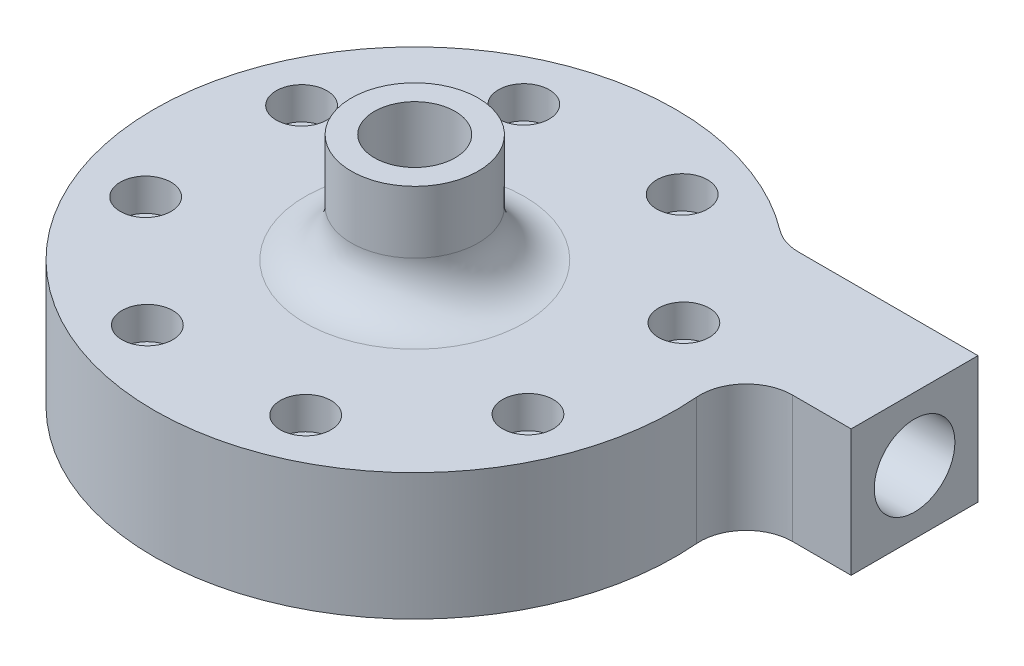
SolidWorks part; units mm, degrees
material "1060 Alloy"
ref_plane "Front" through (0, 0, 0) normal (0, 0, 1) x (1, 0, 0)
ref_plane "Top" through (0, 0, 0) normal (0, 1, 0) x (1, 0, 0)
ref_plane "Right" through (0, 0, 0) normal (1, 0, 0) x (0, 0, -1)
sketch "Sketch1" plane through (0, 0, 0) normal (0, 1, 0) x (1, 0, 0)
  line L0 (0, 0) -> (2.6693, 30.5101) construction
  line L1 (2.6693, 30.5101) -> (60.9409, 35.6082) construction
  line L2 (9.0461, 29.2602) -> (60.9409, 29.2602) construction
  line L3 (14.512, 26.9702) -> (60.9409, 22.9082) construction
  line L4 (0, 0) -> (56.2352, -4.9199) construction
  line L5 (14.512, 31.5462) -> (14.512, 29.2602) construction
  line L6 (14.512, 29.2602) -> (14.512, 26.9702) construction
  line L7 (60.9409, 29.2602) -> (60.9409, 35.6082) construction
  line L8 (60.9409, 29.2602) -> (60.9409, 22.9082) construction
  line L9 (78.9409, 29.2602) -> (78.9409, 42.9915)
  line L10 (78.9409, 37.9915) -> (60.9409, 37.9915) construction
  line L11 (78.9409, 37.9915) -> (78.9409, 20.529) construction
  line L12 (78.9409, 20.529) -> (60.9409, 20.529) construction
  line L13 (60.9409, 37.9915) -> (60.9409, 20.529) construction
  line L14 (78.9409, 42.9915) -> (40.0937, 42.9915)
  line L15 (78.9409, 29.2602) -> (78.9409, 15.529)
  line L16 (78.9409, 15.529) -> (66.2196, 15.529)
  arc A0 (34.06, 45.0169) -> (56.2543, 4.6969) centre (0, 0) ccw
  circle A1 centre (0, 0) radius 30.6267 construction
  arc A2 (66.2196, 15.529) -> (56.2543, 4.6969) centre (66.2196, 5.529) ccw
  arc A3 (40.0937, 42.9915) -> (34.06, 45.0169) centre (40.0937, 52.9915) cw
  dimension "D1" = 112.9
  dimension "D2" = 61.2534
  dimension "D13" = 10
  dimension "D4" = 2.286
  dimension "D3" = 2.29
  dimension "D5" = 5
  dimension "D6" = 5
  dimension "D7" = 5
  dimension "D8" = 12.7
  dimension "D9" = 17.4625
  dimension "D10" = 18
  dimension "D11" = 5
  dimension "D12" = 5
extrude "main body" add sketch "Sketch1" along normal blind 27.4625
ref_plane "body midsection" through (0, 13.7313, 0) normal (0, 1, 0) x (1, 0, 0)
sketch "Sketch2" plane through (0, 0, 0) normal (0, 0, 1) x (1, 0, 0)
  line L0 (0, 27.4625) -> (0, 0) construction
  line L1 (56.45, 27.4625) -> (-56.45, 27.4625) construction
  line L2 (0, 27.4625) -> (5.4102, 27.4625)
  line L3 (0, 12.1864) -> (30.6267, 12.1864) construction
  line L4 (30.6267, 15.2761) -> (5.4102, 25.9331)
  line L5 (5.4102, 27.4625) -> (5.4102, 25.9331)
  line L6 (30.6267, 15.2761) -> (30.6267, 0)
  line L7 (30.6267, 15.2761) -> (30.6267, 12.1864) construction
  line L8 (58.025, 13.7313) -> (-58.025, 13.7313) construction
  line L10 (-56.45, 0) -> (56.45, 0) construction
  line L11 (30.6267, 0) -> (0, 0)
  line L12 (0, 0) -> (0, 27.4625)
  line L13 (30.6267, 13.7313) -> (26.6319, 13.7313) construction
  line L14 (0, 13.7313) -> (26.6319, 13.7313) construction
  line L15 (26.6319, 13.7313) -> (26.6319, 16.9644) construction
  line L16 (26.6319, 16.9644) -> (0, 16.9644) construction
  dimension "D1" = 30.6267
  dimension "D3" = 26.6319
  dimension "D5" = 5.4102
  dimension "D2" = 4.778
  dimension "D6" = 13.7467
revolve "main chamber" cut sketch "Sketch2" angle 360 about L12
sketch "Sketch4" plane through (0, 0, 0) normal (0, 0, 1) x (1, 0, 0)
  line L0 (5.4102, 27.4625) -> (5.4102, 35.9331)
  line L2 (5.4102, 35.9331) -> (8.7313, 35.9331)
  line L3 (8.7313, 35.9331) -> (8.7313, 50.9331)
  line L4 (8.7313, 50.9331) -> (13.7313, 50.9331)
  line L5 (13.7313, 50.9331) -> (13.7313, 37.4625)
  line L7 (0, 0) -> (0, 49.2593) construction
  line L8 (56.45, 0) -> (-56.45, 0) construction
  line L9 (5.4102, 25.9331) -> (-5.4102, 25.9331) construction
  line L10 (5.4102, 27.4625) -> (23.7313, 27.4625)
  arc A0 (13.7313, 37.4625) -> (23.7313, 27.4625) centre (23.7313, 37.4625) ccw
  dimension "D5" = 10
  dimension "D1" = 10
  dimension "D2" = 8.7313
  dimension "D3" = 5
  dimension "D4" = 15
revolve "inlet" add sketch "Sketch4" angle 360 about L7
sketch "Sketch3" plane through (0, 13.7313, 0) normal (0, 1, 0) x (1, 0, 0)
  line L0 (2.6693, 30.5101) -> (60.9409, 35.6082)
  line L2 (60.9409, 29.2602) -> (2.5599, 29.2602)
  line L3 (0, 0) -> (2.6693, 30.5101) construction
  line L4 (2.5599, 29.2602) -> (2.6693, 30.5101)
  line L5 (60.9409, 35.6082) -> (60.9409, 37.9915)
  line L6 (60.9409, 37.9915) -> (78.9409, 37.9915)
  line L7 (78.9409, 37.9915) -> (78.9409, 29.2602)
  line L8 (78.9409, 29.2602) -> (60.9409, 29.2602)
revolve "expansion cone and outlet" cut sketch "Sketch3" angle 360 about L2
sketch "Sketch5" plane through (0, 27.4625, 0) normal (0, 1, 0) x (1, 0, 0)
  line L1 (16.6948, 41.1957) -> (40.9348, 17.3248) construction
  line L3 (9.0461, 29.2602) -> (60.9409, 29.2602) construction
  circle A0 centre (0, 0) radius 44.45 construction
  circle A1 centre (40.9348, 17.3248) radius 2.9766
  circle A2 centre (0, 0) radius 44.45 construction
  circle A3 centre (41.1957, -16.6948) radius 2.9766
  circle A4 centre (0, 0) radius 44.45 construction
  circle A5 centre (17.3248, -40.9348) radius 2.9766
  circle A6 centre (0, 0) radius 44.45 construction
  circle A7 centre (-16.6948, -41.1957) radius 2.9766
  circle A8 centre (0, 0) radius 44.45 construction
  circle A9 centre (-40.9348, -17.3248) radius 2.9766
  circle A10 centre (0, 0) radius 44.45 construction
  circle A11 centre (-41.1957, 16.6948) radius 2.9766
  circle A12 centre (0, 0) radius 44.45 construction
  circle A13 centre (-17.3248, 40.9348) radius 2.9766
  circle A14 centre (0, 0) radius 44.45 construction
  circle A15 centre (16.6948, 41.1957) radius 2.9766
  point P5 (28.8148, 29.2602)
  point P30 (0, 0)
  dimension "D1" = 88.9
  dimension "D2" = 5.9531
  dimension "D4" = 8
sketch "Sketch6" plane through (0, 27.4625, 0) normal (0, 1, 0) x (1, 0, 0)
  circle A0 centre (40.9348, 17.3248) radius 5.5
  circle A1 centre (41.1957, -16.6948) radius 5.5
  circle A2 centre (17.3248, -40.9348) radius 5.5
  circle A3 centre (-16.6948, -41.1957) radius 5.5
  circle A4 centre (-40.9348, -17.3248) radius 5.5
  circle A5 centre (-41.1957, 16.6948) radius 5.5
  circle A6 centre (-17.3248, 40.9348) radius 5.5
  circle A7 centre (16.6948, 41.1957) radius 5.5
  point P19 (0, 0)
  dimension "D1" = 11
  dimension "D2" = 8
ref_plane "exit axial plane" through (0, 0, -29.2602) normal (0, 0, -1) x (-1, 0, 0)
extrude "bolt clearances" cut sketch "Sketch5" against normal through all
extrude "bolt head clearance" cut sketch "Sketch6" against normal blind 7
equation "\"bearing OD\"= 30mm"
equation "\"bearing ID\"= 10mm"
equation "\"bearing depth\"= 9mm"
equation "\"bearing outer race thickness\"= 1mm"
equation "\"bearing inner race thickness\"= 1mm"
equation "\"bearing bore\"= \"bearing depth\" + 1mm"
equation "\"z\"= 8 \t\t\t'number of blades"
equation "\"de\"= 0.426in\t\t\t'entrance eye diameter"
equation "\"d2\"= 2.097in \t\t\t'outer diameter of the impeller"
equation "\"d_exit\"= 0.18in \t\t'volute throat aka D4"
equation "\"theta\"= 25\t\t\t'angle of blades from inner to outer "
equation "\"b2\"= .07in\t\t\t\t\t\t\t'tip height from disc surface at d2"
equation "\"b1\"= \"b2\" + (\"d2\"/2 - \"de\"/2)*sin(\"theta\") \t\t\t'tip height from disc surface at inlet eye"
equation "\"s\"=\"ce\" - \"z\"*\"s_open\""
equation "\"impeller upper clearance\"= .5mm"
equation "\"impeller horizontal clearance\"= (\"d2\"*1.15 - \"d2\")/2 \t\t'clearance based on D2-D3 ratio for circular volute, ranges 1.15 to 1.2"
equation "\"impeller bottom clearance\"= .5mm"
equation "\"impeller base thickness\"= 2mm"
equation "\"impeller dowel diameter\"= 2mm"
equation "\"impeller bolt head diameter\"= \"m4 head bore diameter\""
equation "\"impeller bolt head depth\"= 4mm"
equation "\"impeller bolt stop depth\"= 3mm"
equation "\"impeller bolt bore\"= \"m4 clearance\""
equation "\"impeller shaft bore depth\"= 12mm"
equation "\"impeller shaft bore\"= 8mm"
equation "\"impeller boss depth\"= \"impeller shaft bore depth\"+\"impeller bolt stop depth\"+\"impeller bolt head depth\"-\"impeller base thickness\""
equation "\"impeller boss diameter\"= \"upper seal ID\""
equation "\"impeller dowel length\"= 2mm*2 + \"impeller shaft bore\""
equation "\"coupler motor shaft hole ID\"= 8mm"
equation "\"coupler OD\"= 17mm"
equation "\"coupler length\"= 25mm"
equation "\"motor OD\"= 64mm"
equation "\"motor shaft diameter\"= 8mm"
equation "\"motor shaft pride\"= 32mm"
equation "\"motor to bearing plate distance\"= \"motor shaft pride\" + 2mm +\"coupler length\"/2"
equation "\"square plate bolt bore\"= 8mm"
equation "\"square plate bolt head diameter\"= 13.5mm"
equation "\"square plate bolt head depth\"= 8mm"
equation "\"square plate bolt pattern diameter\"= 3.5in"
equation "\"motor mount center bore\"= \"coupler OD\"+ 4mm"
equation "\"motor mount post radius\"= ( 3 * \"square plate bolt bore\" ) / 2"
equation "\"motor mount m4 screw hole diameter\"= 4mm"
equation "\"motor mount m4 head diameter\"= 7.25mm"
equation "\"motor mount m4 head depth\"= 4mm"
equation "\"motor mount m4 pattern diamater\"= 30mm"
equation "\"motor mount plate thickness\"= 8mm + \"motor mount m4 head depth\""
equation "\"bearing plate stop ID\"= \"bearing OD\" - 4mm"
equation "\"bearing plate stop depth\"= 3mm"
equation "\"bearing plate thickness\"= \"bearing bore\" + \"bearing plate stop depth\" + \"shaft bearing stop length\""
equation "\"shaft coupler section diameter\"= 8mm"
equation "\"shaft coupler section length\"= \"motor to bearing plate distance\" - \"motor shaft pride\" - 2mm"
equation "\"shaft bearing section diameter\"= \"bearing ID\""
equation "\"shaft bearing section length\"= \"bearing plate stop depth\" + \"bearing depth\""
equation "\"shaft bearing stop diameter\"= \"bearing ID\" + 4mm"
equation "\"shaft bearing stop length\"= 3mm"
equation "\"impeller cavity center height\"= \"impeller bottom clearance\" + \"impeller upper clearance\" + \"impeller center height\""
equation "\"impeller cavity diameter\"= 2 * \"impeller horizontal clearance\" + \"d2\" \t\t\t\t\t\t\t\t\t'called D3 analytically"
equation "\"impeller cavity outer height\"= \"impeller bottom clearance\" + \"impeller upper clearance\" + \"impeller base thickness\" + \"b2\" \t\t'this is height at impeller diameter d2, not at d3"
equation "\"impeller housing thickness\"= \"impeller housing exit threaded diameter\" + 2*\"impeller housing outlet grip\""
equation "\"impeller housing diameter\"= \"square plate bolt pattern diameter\" + 2*\"motor mount post radius\""
equation "\"impeller housing bolt count\"= 8"
equation "\"impeller housing bolt diameter\"= \"m6 clearance\""
equation "\"impeller housing bolt pattern diameter\"= 3.5in"
equation "\"impeller housing threaded inlet diameter\"= 0.6875in \t\t'this is the 11/16 drill size for 1/2 npt fitting"
equation "\"impeller housing threaded inlet depth\"= 15mm"
equation "\"impeller housing exit threaded diameter\"= 0.6875in \t\t'this is the 11/16 drill size for 1/2 npt fitting"
equation "\"impeller housing exit threaded depth\"= 18mm"
equation "\"impeller housing diffuser conical angle\"=10"
equation "\"impeller housing diffuser tangent angle\"=5"
equation "\"impeller housing diffuser final diameter\"= .5in"
equation "\"impeller housing outlet grip\"= 5mm"
equation "\"D1@Sketch1\"=\"impeller housing diameter\""
equation "\"D2@Sketch1\"=\"impeller cavity diameter\""
equation "\"D4@Sketch1\"=\"d_exit\"/2"
equation "\"D5@Sketch1\"=\"impeller housing diffuser tangent angle\""
equation "\"D6@Sketch1\"=\"impeller housing diffuser conical angle\"/2"
equation "\"D7@Sketch1\"=\"impeller housing diffuser conical angle\"/2"
equation "\"D8@Sketch1\"=\"impeller housing diffuser final diameter\""
equation "\"D9@Sketch1\"=\"impeller housing exit threaded diameter\""
equation "\"D10@Sketch1\"=\"impeller housing exit threaded depth\""
equation "\"D11@Sketch1\"=\"impeller housing outlet grip\""
equation "\"D12@Sketch1\"=\"impeller housing outlet grip\""
equation "\"D1@main body\" = \"impeller housing thickness\""
equation "\"D1@Sketch2\"=\"impeller cavity diameter\"/2"
equation "\"D3@Sketch2\"= \"d2\" / 2"
equation "\"D2@Sketch2\"=\"impeller cavity outer height\""
equation "\"D5@Sketch2\"=\"de\"/2"
equation "\"D6@Sketch2\" = \"impeller center height\" + \"impeller bottom clearance\" + \"impeller upper clearance\""
equation "\"de_length\"= 10mm\t\t'entrance eye consistent length"
equation "\"D2@Sketch4\"=\"impeller housing threaded inlet diameter\"/2"
equation "\"D3@Sketch4\"=\"impeller housing outlet grip\""
equation "\"D4@Sketch4\"=\"impeller housing threaded inlet depth\""
equation "\"D1@Sketch5\"=\"impeller housing bolt pattern diameter\""
equation "\"D2@Sketch5\"=\"m6 clearance\""
equation "\"end mill size\"= 0.375in\t'for 3/8 endmill"
equation "\"ae\"= 3.14*(\"de\"^2)/4\t\t'entrance eye area'"
equation "\"ce\"= 3.14*\"de\"\t\t'entrance eye circumference"
equation "\"av_ratio\"= .325\t\t'ratio of av/ae at N_s of 470, range is .275 to .375, .325 ideal. High ratio means bigger area means smaller blades"
equation "\"av\"= \"ae\"*\"av_ratio\"\t\t'area between just two blades"
equation "\"s_open\"= \"av\"/\"b1\"\t\t'width of open area"
equation "\"impeller center height\"= \"impeller base thickness\" + \"b1\"\t'impeller height at de"
equation "\"impeller outer height\"= \"impeller base thickness\" + \"b2\"\t'impeller height at de"
equation "\"shaft impeller section diameter\"= \"impeller shaft bore\""
equation "\"shaft impeller section length\"= \"upper seal plate thickness\" + \"upper seal plate riser\" + \"impeller bottom clearance\" + \"impeller base thickness\" - \"impeller bolt head depth\" - \"impeller bolt stop depth\""
equation "\"m6 clearance\"= 0.234375in\t'this is 15/64 bit = 5.95mm, could use 6mm bit, B bit for 6.04mm or 1/4 bit for 6.35mm"
equation "\"m6 tap\"= 5mm\t\t\t'5mm is appropriate, could use 13/64 or #5,6,7"
equation "\"m6 head bore diameter\"= 11mm\t\t"
equation "\"m6 head bore depth\"= 7mm\t'actual is 6mm"
equation "\"m8 clearance\"= 0.3125in\t'this is 5/16in for 7.93mm, could use 8mm, O,P, or 21/64"
equation "\"m8 tap\"= 0.265625in\t\t'this is 17/64 for 6.746875mm"
equation "\"m8 head bore diameter\"= 14mm"
equation "\"m8 head bore depth\"= 9mm\t'actual is 8mm"
equation "\"D1@Sketch6\"=\"m6 head bore diameter\""
equation "\"D1@bolt head clearance\" = \"m6 head bore depth\""
equation "\"lower seal OD\"= .917in\t\t'this is https://www.mcmaster.com/#9281k121/=174001b"
equation "\"lower seal ID\"= .375in"
equation "\"lower seal depth\"= .625in + .218in"
equation "\"lower seal bore\"= \"lower seal depth\" + 1mm"
equation "\"upper seal OD\"= 1.125in\t'this is https://www.mcmaster.com/#5154t33/=173zuau, needs to be visually inspected before machining!"
equation "\"upper seal ID\"= 0.625in"
equation "\"upper seal depth\"= .25in\t'aka height; these values need to be confirmed by inspection!! We may want to compress the height."
equation "\"upper seal bore\"= \"upper seal depth\" + 1mm"
equation "\"big o-ring thickness\"= .139in"
equation "\"big o-ring OD\"= 2.734in"
equation "\"big o-ring ID\"= 3.012in"
equation "\"big o-ring groove depth\"= \"big o-ring thickness\"*4/5"
equation "\"lower seal plate lip depth\"= 2mm"
equation "\"lower seal plate lip ID\"= \"lower seal OD\" - 3mm"
equation "\"lower seal plate thickness\"= \"lower seal plate lip depth\" + \"lower seal bore\""
equation "\"shaft lower seal section diameter\"= \"lower seal ID\""
equation "\"shaft lower seal section length\"= \"lower seal plate thickness\" + 1mm"
equation "\"upper seal plate thickness\"= \"upper seal plate pressure hole diameter\"*3"
equation "\"upper seal plate lip ID\"= \"upper seal OD\" - 3mm"
equation "\"upper seal plate riser\"= \"impeller housing thickness\"/2 - \"b2\"/2 - \"impeller base thickness\" - \t\"impeller bottom clearance\"\t\t\t'this offsets the gap under the housing"
equation "\"upper seal plate pressure hole diameter\"= .125in\t'this is 1/8 drill "
equation "\"upper seal plate pressure tap diameter\"= .328125in \t'this is 21/64 drill for a 1/8 ANPT tap"
equation "\"upper seal plate pressure tap grip\"= 4mm\t\t'this is the area around the tap so it doesn't crack"
equation "\"upper seal plate pressure tap depth\"= 12"
equation "\"m4 clearance\"= 0.171875in \t'this is 11/64 bit for 4.36mm"
equation "\"m4 tap\"= 0.125in\t\t'this is 1/8 bit for 3.17mm"
equation "\"m4 head bore diameter\"= 7.5mm"
equation "\"m4 head bore depth\"= 5mm\t'actual is ~4mm"
